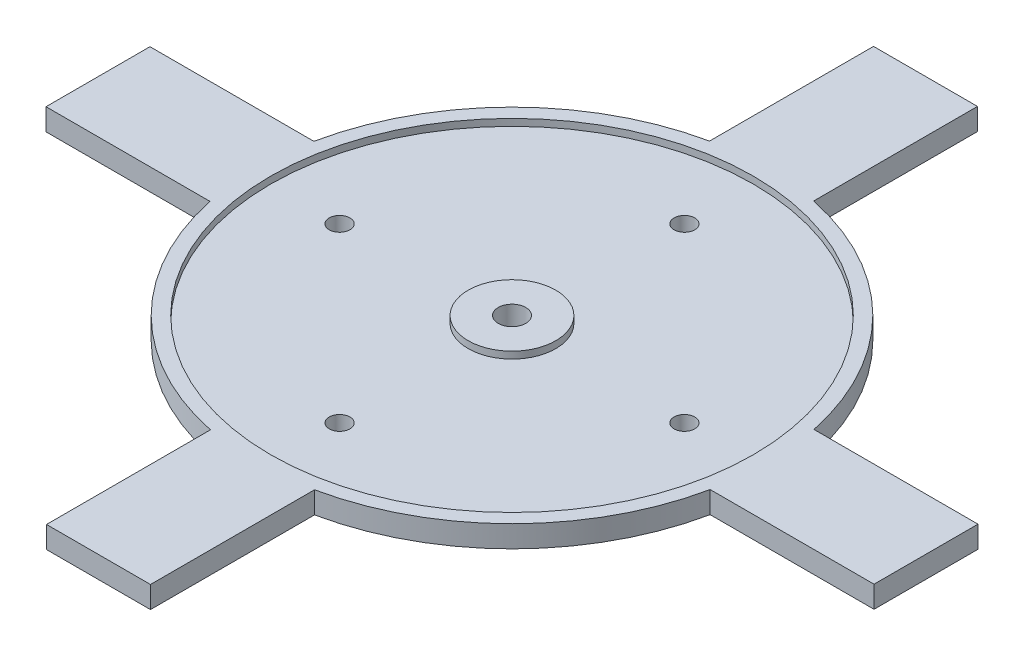
SolidWorks part; units mm, degrees
ref_plane "Front Plane" through (0, 0, 0) normal (0, 0, 1) x (1, 0, 0)
ref_plane "Top Plane" through (0, 0, 0) normal (0, 1, 0) x (1, 0, 0)
ref_plane "Right Plane" through (0, 0, 0) normal (1, 0, 0) x (0, 0, -1)
ref_axis "Axis1" through (0, 3.3161, 0) along (0, -1, 0)
sketch "Sketch1" plane through (0, 0, 0) normal (0, 1, 0) x (1, 0, 0)
  circle A0 centre (0, 0) radius 37
extrude "Boss-Extrude1" add sketch "Sketch1" along normal blind 3.1582 contours A0
sketch "Sketch13" plane through (0, 0, 0) normal (0, 0, 1) x (1, 0, 0)
  line L0 (37, 3.1582) -> (-37, 3.1582) construction
  line L1 (0, 3.1582) -> (7.5757, 3.1582)
  line L2 (0, 3.1582) -> (0, 0)
  line L3 (0, 0) -> (7.5757, 0)
  line L4 (7.5757, 3.1582) -> (7.5757, 0)
  line L5 (-37, 0) -> (37, 0) construction
  line L7 (0, 3.1582) -> (-7.5, 3.1582)
  line L8 (0, 3.1582) -> (0, 0)
  line L9 (0, 0) -> (-7.5, 0)
  line L10 (-7.5, 3.1582) -> (-7.5, 0)
extrude "Boss-Extrude2" add sketch "Sketch13" along normal blind 60 contours L8 L9 L10 L7 | L2 L3 L4 L1
pattern_circular "CirPattern1" count 4 over 360 about axis through (0, 3.3161, 0) along (0, -1, 0) of "Boss-Extrude2"
sketch "Sketch2" plane through (0, 3.1582, 0) normal (0, 1, 0) x (1, 0, 0)
  circle A0 centre (0, 0) radius 6.35
  circle A1 centre (0, 0) radius 35
extrude "Cut-Extrude1" cut sketch "Sketch2" against normal blind 1
sketch "Sketch17" plane through (0, 3.1582, 0) normal (0, 1, 0) x (1, 0, 0)
  circle A0 centre (0, 0) radius 2
extrude "Cut-Extrude2" cut sketch "Sketch17" against normal blind 10
sketch "Sketch19" plane through (0, 3.1582, 0) normal (0, 1, 0) x (1, 0, 0)
  line L0 (0, 0) -> (0, 25)
  circle A0 centre (0, 25) radius 1.5
extrude "Cut-Extrude3" cut sketch "Sketch19" against normal blind 10 contours A0
pattern_circular "CirPattern2" count 4 over 360 about axis through (0, 3.3161, 0) along (0, -1, 0) of "Cut-Extrude3"
